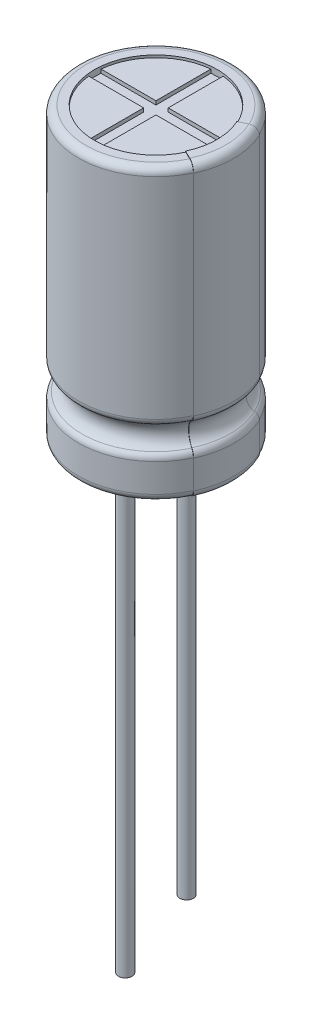
SolidWorks part; units mm, degrees
note: The reader was unsure of these and kept them because the rebuilt part matched: shared geometry of "Sketch7<4>".
ref_plane "Front Plane" through (0, 0, 0) normal (0, 0, 1) x (1, 0, 0)
ref_plane "Top Plane" through (0, 0, 0) normal (0, 1, 0) x (1, 0, 0)
ref_plane "Right Plane" through (0, 0, 0) normal (1, 0, 0) x (0, 0, -1)
sketch "Sketch1" plane through (0, 0, 0) normal (0, 0, 1) x (1, 0, 0)
  line L8 (0, 0.6) -> (2.55, 0.6)
  line L9 (2.55, 0.6) -> (2.55, 0.4)
  line L10 (2.55, 0.4) -> (2.85, 0.4)
  line L11 (3.15, 0.7) -> (3.15, 1.8569)
  line L12 (2.85, 12.2) -> (2.5, 12.2)
  line L13 (2.5, 12.2) -> (2.5, 11.95)
  line L14 (2.5, 11.95) -> (0, 11.95)
  line L15 (0, 11.95) -> (0, 0.6)
  line L16 (1.2518, 2.6) -> (5.492, 2.6) construction
  line L17 (3.15, 3.3431) -> (3.15, 11.9)
  arc A0 (2.85, 0.4) -> (3.15, 0.7) centre (2.85, 0.7) ccw
  arc A1 (3.15, 11.9) -> (2.85, 12.2) centre (2.85, 11.9) ccw
  arc A2 (3.0116, 3.0903) -> (3.0116, 2.1097) centre (3.325, 2.6) ccw
  arc A3 (3.15, 1.8569) -> (3.0116, 2.1097) centre (2.85, 1.8569) ccw
  arc A4 (3.15, 3.3431) -> (3.0116, 3.0903) centre (2.85, 3.3431) cw
  dimension "D8" = 0.3
  dimension "D11" = 1.1639
  dimension "D12" = 0.3
  dimension "D1" = 11.35
  dimension "D2" = 0.2
  dimension "D3" = 0.6
  dimension "D4" = 2.5
  dimension "D5" = 0.65
  dimension "D6" = 0.25
  dimension "D7" = 0.6
  dimension "D9" = 2.2
  dimension "D10" = 3.325
revolve "Revolve1" add sketch "Sketch1" angle 360 about L15
sketch "Sketch2" plane through (0, 11.95, 0) normal (0, 1, 0) x (1, 0, 0)
  line L0 (-0.25, 0.25) -> (-0.25, 2.4875)
  line L2 (0.25, -2.4875) -> (0.25, -0.25)
  line L4 (-0.25, -2.4875) -> (-0.25, -0.25)
  line L5 (0.25, 0.25) -> (0.25, 2.4875)
  line L7 (2.4875, -0.25) -> (0.25, -0.25)
  line L9 (2.4875, 0.25) -> (0.25, 0.25)
  line L13 (-0.25, -0.25) -> (-2.4875, -0.25)
  line L16 (-0.25, 0.25) -> (-2.4875, 0.25)
  arc A0 (0.25, -2.4875) -> (2.4875, -0.25) centre (0, 0) ccw
  arc A1 (2.4875, 0.25) -> (0.25, 2.4875) centre (0, 0) ccw
  arc A2 (-0.25, 2.4875) -> (-2.4875, 0.25) centre (0, 0) ccw
  arc A3 (-2.4875, -0.25) -> (-0.25, -2.4875) centre (0, 0) ccw
  dimension "D3" = 2.5
  dimension "D1" = 0.5
  dimension "D2" = 0.5
extrude "Boss-Extrude1" add sketch "Sketch2" along normal blind 0.15 separate body
sketch "Sketch3" plane through (0, 0.6, 0) normal (0, -1, 0) x (1, 0, 0)
  circle A0 centre (0, 0) radius 1.8
  ellipse E0 centre (0, 0) end of major axis (-1.67, 0) minor radius 0.9
  dimension "D1" = 3.6
extrude "Boss-Extrude2" add sketch "Sketch3" along normal blind 0.6 separate body
sketch "Sketch4" plane through (0, 0.6, 0) normal (0, -1, 0) x (1, 0, 0)
sketch "Sketch5" plane through (0, 0, 0) normal (0, 0, 1) x (1, 0, 0)
  line L8 (2.5, 12.2) -> (2.85, 12.2)
  line L10 (3.15, 3.3431) -> (3.15, 11.9) construction
  line L11 (3.15, 11.9) -> (3.15, 3.3431)
  line L12 (2.5, 12.2) -> (2.55, 0.4)
  line L13 (2.55, 0.4) -> (2.85, 0.4)
  line L14 (0, 0) -> (0, 15.0032) construction
  line L15 (2.4799, 12.22) -> (2.5301, 0.38)
  line L16 (3.15, 0.7) -> (3.15, 1.8569)
  line L17 (2.5301, 0.38) -> (2.85, 0.38)
  line L18 (3.17, 0.7) -> (3.17, 1.8569)
  line L19 (3.17, 11.9) -> (3.17, 3.3431)
  line L20 (2.4799, 12.22) -> (2.85, 12.22)
  arc A5 (2.85, 12.2) -> (3.15, 11.9) centre (2.85, 11.9) cw
  arc A6 (2.85, 0.4) -> (3.15, 0.7) centre (2.85, 0.7) ccw construction
  arc A7 (3.15, 1.8569) -> (3.0116, 2.1097) centre (2.85, 1.8569) ccw
  arc A8 (3.15, 3.3431) -> (3.0116, 3.0903) centre (2.85, 3.3431) cw
  arc A9 (3.0116, 3.0903) -> (3.0116, 2.1097) centre (3.325, 2.6) ccw
  arc A10 (3.15, 0.7) -> (2.85, 0.4) centre (2.85, 0.7) cw
  arc A11 (3.17, 0.7) -> (2.85, 0.38) centre (2.85, 0.7) cw
  arc A12 (3.17, 1.8569) -> (3.0223, 2.1265) centre (2.85, 1.8569) ccw
  arc A13 (3.0223, 3.0735) -> (3.0223, 2.1265) centre (3.325, 2.6) ccw
  arc A14 (3.17, 3.3431) -> (3.0223, 3.0735) centre (2.85, 3.3431) cw
  arc A15 (2.85, 12.22) -> (3.17, 11.9) centre (2.85, 11.9) cw
  dimension "D1" = 0.02
revolve "Revolve3" add sketch "Sketch5" angle 25 about L14
sketch "Sketch7" plane through (0, 0.6, 0) normal (0, -1, 0) x (1, 0, 0)
  line L0 (-1.4523, 0) -> (1.4342, 0) construction
  line L1 (0, 0) -> (0, 0.7626) construction
  circle A0 centre (-1.25, 0) radius 0.275
  circle A2 centre (1.25, 0) radius 0.275
  dimension "D2" = 0.55
  dimension "D1" = 1.25
extrude "Boss-Extrude3" add sketch "Sketch7" along normal blind 19.6 contours A0
extrude "Boss-Extrude4" add sketch "Sketch7<4>" along normal blind 15.6 contours A2
sketch "Sketch7<4>" plane through (0, 0.6, 0) normal (0, -1, 0) x (1, 0, 0) same geometry as "Sketch7"
